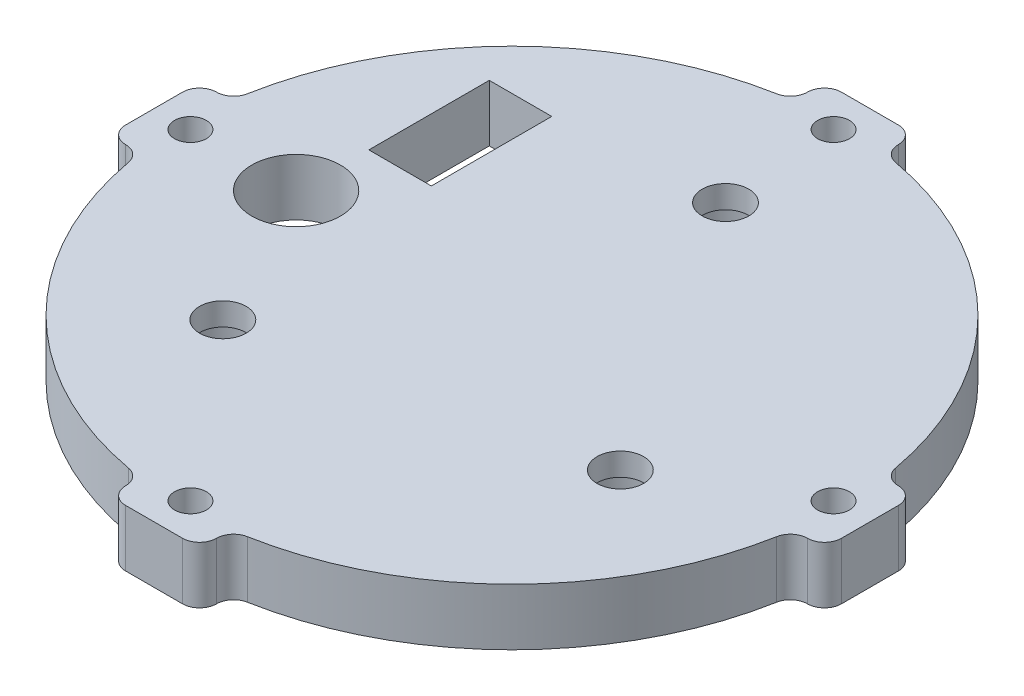
SolidWorks part; units mm, degrees
material "ABS"
ref_plane "Front Plane" through (0, 0, 0) normal (0, 0, 1) x (1, 0, 0)
ref_plane "Top Plane" through (0, 0, 0) normal (0, 1, 0) x (1, 0, 0)
ref_plane "Right Plane" through (0, 0, 0) normal (1, 0, 0) x (0, 0, -1)
sketch "Sketch1" plane through (0, 0, 0) normal (0, 1, 0) x (1, 0, 0)
  circle A0 centre (0, 0) radius 29
  dimension "D1" = 58
extrude "Boss-Extrude1" add sketch "Sketch1" along normal mid plane 5
sketch "Sketch3" plane through (0, 0, 0) normal (0, 0, 1) x (1, 0, 0)
  line L0 (29, 2.5) -> (-29, 2.5) construction
  line L1 (4, -2.5) -> (-4, -2.5)
  line L2 (4, -2.5) -> (4, 2.5)
  line L3 (4, 2.5) -> (-4, 2.5)
  line L4 (-4, -2.5) -> (-4, 2.5)
  line L5 (4, -2.5) -> (-4, 2.5) construction
  line L6 (4, 2.5) -> (-4, -2.5) construction
  point P0 (0, 0)
  dimension "D1" = 8
extrude "Boss-Extrude2" add sketch "Sketch3" along normal blind 31.5
sketch "Sketch5" plane through (0, 2.5, 0) normal (0, 1, 0) x (1, 0, 0)
  circle A0 centre (0, -28.3) radius 1.4
  dimension "D1" = 2.8
  dimension "D2" = 28.3
extrude "Cut-Extrude1" cut sketch "Sketch5" against normal through all
fillet "Fillet2" radius 1.5 4 edges at (4, 0, 28.7228) (-4, 0, 28.7228) (-4, 0, 31.5) (4, 0, 31.5)
pattern_circular "CirPattern1" count 4 over 360 about axis through (0, 2.5, 0) along (0, -1, 0) of "Boss-Extrude2", "Cut-Extrude1", "Fillet2"
sketch "Sketch6" plane through (0, 2.5, 0) normal (0, 1, 0) x (1, 0, 0)
  circle A0 centre (-19, 0) radius 3.9
  dimension "D1" = 7.8
  dimension "D2" = 19
extrude "Cut-Extrude2" cut sketch "Sketch6" against normal through all
sketch "Sketch7" plane through (0, 2.5, 0) normal (0, 1, 0) x (1, 0, 0)
  line L1 (-18.9, 6.3) -> (-13.4, 6.3)
  line L2 (-18.9, 6.3) -> (-18.9, 16.9)
  line L3 (-18.9, 16.9) -> (-13.4, 16.9)
  line L4 (-13.4, 6.3) -> (-13.4, 16.9)
  line L5 (-18.9, 6.3) -> (-13.4, 16.9) construction
  line L6 (-18.9, 16.9) -> (-13.4, 6.3) construction
  point P0 (-16.15, 11.6)
  dimension "D1" = 5.5
  dimension "D2" = 10.6
  dimension "D3" = 13.4
  dimension "D4" = 6.3
extrude "Cut-Extrude3" cut sketch "Sketch7" against normal through all
sketch "Sketch8" plane through (0, -2.5, 0) normal (0, -1, 0) x (1, 0, 0)
  circle A0 centre (0.8086, -17.9818) radius 2.05
  circle A1 centre (16.5691, 7.0332) radius 2.05
  circle A2 centre (-12.3734, 13.0729) radius 2.05
  dimension "D1" = 4.1
extrude "Cut-Extrude4" cut sketch "Sketch8" against normal through all
sketch "Sketch9" plane through (0, -2.5, 0) normal (0, -1, 0) x (-1, 0, 0)
  circle A0 centre (-0.8086, 17.9818) radius 3.75
  circle A1 centre (12.3734, -13.0729) radius 3.75
  circle A2 centre (-16.5691, -7.0332) radius 3.75
  dimension "D1" = 7.5
extrude "Cut-Extrude5" cut sketch "Sketch9" against normal blind 3
